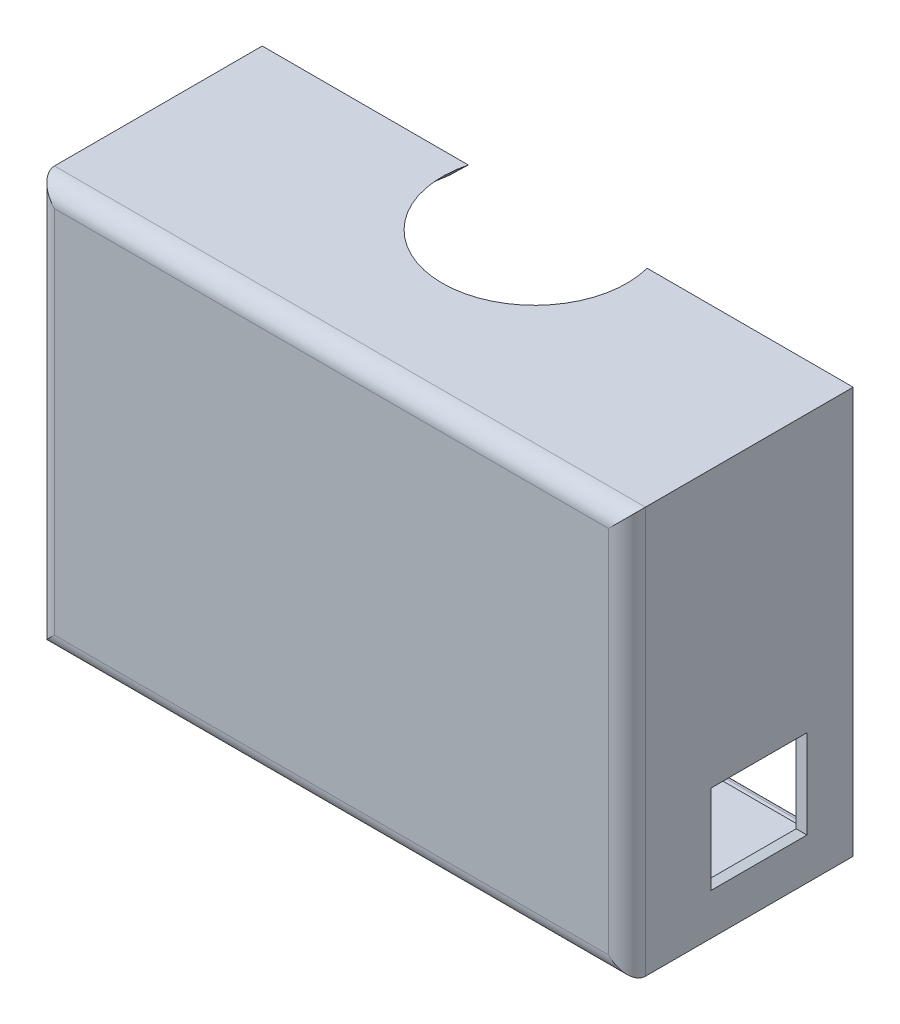
SolidWorks part; units mm, degrees
ref_plane "Front Plane" through (0, 0, 0) normal (0, 0, 1) x (1, 0, 0)
ref_plane "Top Plane" through (0, 0, 0) normal (0, 1, 0) x (1, 0, 0)
ref_plane "Right Plane" through (0, 0, 0) normal (1, 0, 0) x (0, 0, -1)
sketch "Sketch1" plane through (0, 0, 0) normal (0, 0, 1) x (1, 0, 0)
  line L1 (-35.1511, 30.4555) -> (41.0489, 30.4555)
  line L2 (-35.1511, 30.4555) -> (-35.1511, -20.3445)
  line L3 (-35.1511, -20.3445) -> (41.0489, -20.3445)
  line L4 (41.0489, 30.4555) -> (41.0489, -20.3445)
  line L5 (-37.6911, 32.9955) -> (43.5889, 32.9955)
  line L6 (-37.6911, 32.9955) -> (-37.6911, -22.8845)
  line L7 (-37.6911, -22.8845) -> (43.5889, -22.8845)
  line L8 (43.5889, 32.9955) -> (43.5889, -22.8845)
  dimension "D1" = 50.8
  dimension "D2" = 76.2
  dimension "D3" = 2.54
  dimension "D4" = 2.54
  dimension "D5" = 2.54
  dimension "D6" = 2.54
extrude "Boss-Extrude1" add sketch "Sketch1" along normal blind 28.575
sketch "Sketch2" plane through (0, 0, 28.575) normal (0, 0, 1) x (1, 0, 0)
  line L1 (-37.6911, 32.9955) -> (43.5889, 32.9955)
  line L2 (-37.6911, 32.9955) -> (-37.6911, -22.8845)
  line L3 (-37.6911, -22.8845) -> (43.5889, -22.8845)
  line L4 (43.5889, 32.9955) -> (43.5889, -22.8845)
extrude "Boss-Extrude2" add sketch "Sketch2" along normal blind 2.54
sketch "Sketch5" plane through (43.5889, 0, 0) normal (1, 0, 0) x (0, 0, -1)
  line L1 (-19.558, -4.9775) -> (-6.35, -4.9775)
  line L2 (-19.558, -4.9775) -> (-19.558, -17.1695)
  line L3 (-19.558, -17.1695) -> (-6.35, -17.1695)
  line L4 (-6.35, -4.9775) -> (-6.35, -17.1695)
  line L7 (0, -22.8845) -> (0, 32.9955) construction
  line L9 (-31.115, -22.8845) -> (0, -22.8845) construction
  dimension "D1" = 12.192
  dimension "D2" = 13.208
  dimension "D3" = 5.715
  dimension "D4" = 6.35
extrude "Cut-Extrude1" cut sketch "Sketch5" against normal blind 2.54
sketch "Sketch6" plane through (0, 32.9955, 0) normal (0, 1, 0) x (1, 0, 0)
  line L2 (43.5889, -31.115) -> (43.5889, 0) construction
  line L3 (43.5889, -31.115) -> (-37.6911, -31.115) construction
  circle A0 centre (2.9489, -3.175) radius 12.7
  dimension "D1" = 40.64
  dimension "D3" = 25.4
  dimension "D2" = 27.94
extrude "Cut-Extrude2" cut sketch "Sketch6" against normal blind 2.54
chamfer "Chamfer4" distance 2.54 angle 22.5 4 edges at (41.0489, -17.1695, 12.954) (41.0489, -11.0735, 19.558) (41.0489, -4.9775, 12.954) (41.0489, -11.0735, 6.35) first distance on face at (42.3189, -17.1695, 12.954) first distance on face at (42.3189, -11.0735, 19.558) first distance on face at (42.3189, -4.9775, 12.954) first distance on face at (42.3189, -11.0735, 6.35)
sketch "Sketch8" plane through (0, 0, 0) normal (0, 0, -1) x (-1, 0, 0)
  line L0 (-41.0489, 30.4555) -> (-21.9989, 30.4555)
  line L2 (-41.0489, 30.4555) -> (-41.0489, -20.3445)
  line L3 (-41.0489, -20.3445) -> (35.1511, -20.3445)
  line L4 (35.1511, 30.4555) -> (35.1511, -20.3445)
  line L6 (-42.3189, 31.7255) -> (-42.3189, -21.6145)
  line L7 (-42.3189, -21.6145) -> (36.4211, -21.6145)
  line L8 (36.4211, 31.7255) -> (36.4211, -21.6145)
  line L9 (-41.0489, 30.4555) -> (-15.2456, 30.4555) construction
  line L10 (-42.3189, 31.7255) -> (-21.9989, 31.7255)
  line L11 (35.1511, 30.4555) -> (16.1011, 30.4555)
  line L12 (9.3478, 30.4555) -> (35.1511, 30.4555) construction
  line L13 (36.4211, 31.7255) -> (16.1011, 31.7255)
  line L14 (-21.9989, 31.7255) -> (-21.9989, 30.4555)
  line L15 (16.1011, 31.7255) -> (16.1011, 30.4555)
  dimension "D1" = 19.05
  dimension "D2" = 1.27
  dimension "D3" = 1.27
  dimension "D4" = 1.27
  dimension "D5" = 19.05
  dimension "D6" = 1.27
  dimension "D7" = 1.27
extrude "Cut-Extrude3" cut sketch "Sketch8" against normal blind 2.54
chamfer "Chamfer5" distance 2.54 angle 45 1 edges at (2.9489, 30.4555, 15.875)
fillet "Fillet2" radius 0.762 5 edges at (2.9489, -21.6145, 0) (-36.4211, 5.0555, 0) (42.3189, 5.0555, 0) (32.1589, 31.7255, 0) (-26.2611, 31.7255, 0)
fillet "Fillet3" radius 2.54 4 edges at (-37.6911, 5.0555, 31.115) (2.9489, -22.8845, 31.115) (43.5889, 5.0555, 31.115) (2.9489, 32.9955, 31.115)
